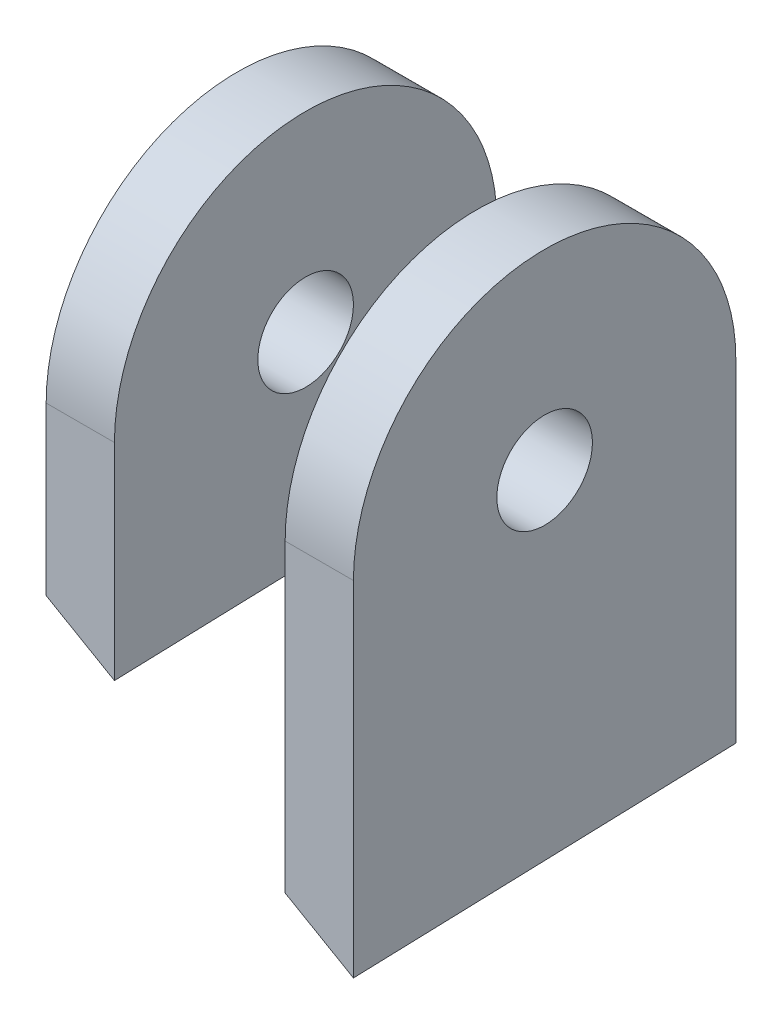
SolidWorks part; units mm, degrees
ref_plane "前视基准面" through (0, 0, 0) normal (0, 0, 1) x (1, 0, 0)
ref_plane "上视基准面" through (0, 0, 0) normal (0, 1, 0) x (1, 0, 0)
ref_plane "右视基准面" through (0, 0, 0) normal (1, 0, 0) x (0, 0, -1)
sketch "草图1" plane through (0, 0, 0) normal (1, 0, 0) x (0, 0, -1)
  line L0 (-28, 0) -> (-28, -100)
  line L1 (28, 0) -> (28, -100)
  line L2 (28, -100) -> (-28, -100)
  arc A0 (28, 0) -> (-28, 0) centre (0, 0) ccw
  circle A1 centre (0, 0) radius 7
extrude "凸台-拉伸1" add sketch "草图1" along normal blind 10 and the other way blind 35
extrude "切除-拉伸1" cut sketch "草图1<2>" against normal blind 25
sketch "草图1<2>" plane through (0, 0, 0) normal (1, 0, 0) x (0, 0, -1) same geometry as "草图1"
sketch "草图2" plane through (-18.9339, -32.7779, -1.0421) normal (0.5, 0.8656, 0.0275) x (-0.7522, 0.4183, 0.5091)
  circle A0 centre (0, 0) radius 145.5562
extrude "切除-拉伸5" cut sketch "草图2" against normal blind 168
